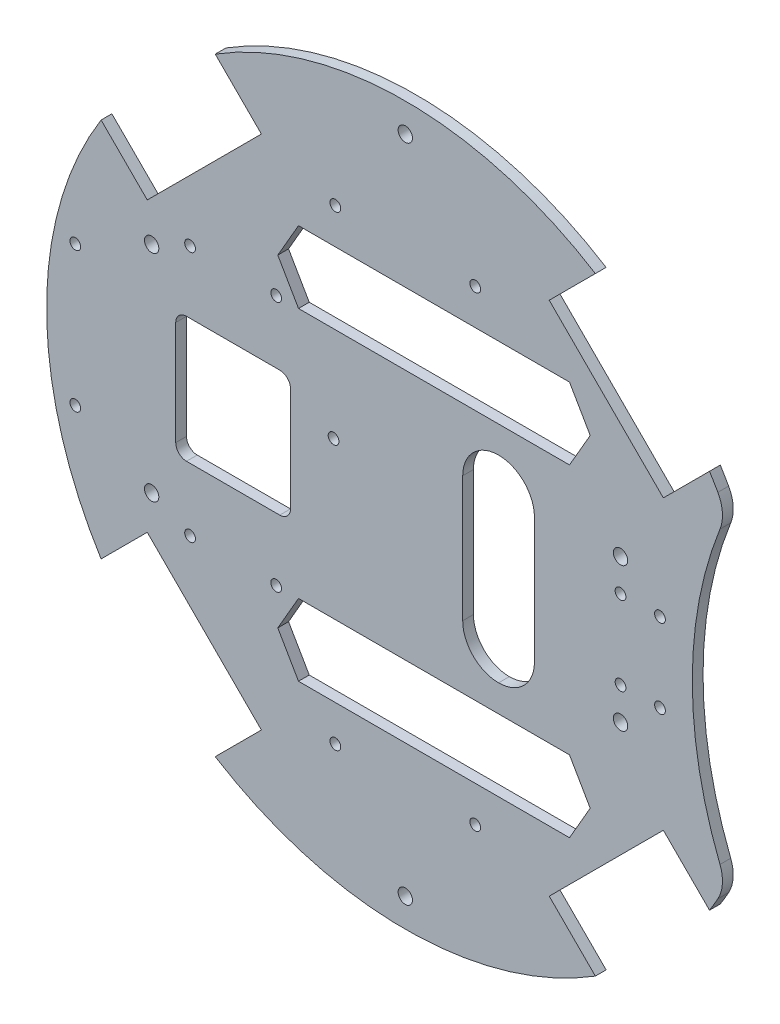
SolidWorks part; units mm, degrees
material "Caoba"
ref_plane "Alzado" through (0, 0, 0) normal (0, 0, 1) x (1, 0, 0)
ref_plane "Planta" through (0, 0, 0) normal (0, 1, 0) x (1, 0, 0)
ref_plane "Vista lateral" through (0, 0, 0) normal (1, 0, 0) x (0, 0, -1)
sketch "Croquis1" plane through (0, 0, 0) normal (0, 0, 1) x (1, 0, 0)
  circle A0 centre (0, 0) radius 100
  dimension "D1" = 200
extrude "Saliente-Extruir1" add sketch "Croquis1" along normal blind 3
sketch "Croquis3" plane through (0, 0, 3) normal (0, 0, 1) x (1, 0, 0)
  line L0 (0, 0) -> (190, 0) construction
  circle A0 centre (190, 0) radius 110
  dimension "D1" = 220
  dimension "D2" = 190
extrude "Cortar-Extruir1" cut sketch "Croquis3" against normal blind 3
fillet "Redondeo1" radius 10 2 edges at (89.4737, -44.6594, 1.5) (89.4737, 44.6594, 1.5)
sketch "Croquis7" plane through (0, 0, 3) normal (0, 0, 1) x (1, 0, 0)
  line L0 (-71.9393, -40.1195) -> (-40.1195, -71.9393)
  line L1 (-71.9393, -40.1195) -> (-89.617, -57.7972)
  line L2 (-40.1195, -71.9393) -> (-57.7972, -89.617)
  line L3 (-89.617, -57.7972) -> (-57.7972, -89.617)
  line L6 (0, -100) -> (0, 100) construction
  line L7 (-100, 0) -> (80, 0) construction
  line L8 (-40.1195, 71.9393) -> (-71.9393, 40.1195)
  line L9 (-40.1195, 71.9393) -> (-57.7972, 89.617)
  line L10 (-57.7972, 89.617) -> (-89.617, 57.7972)
  line L11 (-71.9393, 40.1195) -> (-89.617, 57.7972)
  line L12 (71.9393, 40.1195) -> (40.1195, 71.9393)
  line L13 (71.9393, 40.1195) -> (89.617, 57.7972)
  line L14 (89.617, 57.7972) -> (57.7972, 89.617)
  line L15 (40.1195, 71.9393) -> (57.7972, 89.617)
  line L16 (40.1195, -71.9393) -> (71.9393, -40.1195)
  line L17 (40.1195, -71.9393) -> (57.7972, -89.617)
  line L18 (57.7972, -89.617) -> (89.617, -57.7972)
  line L19 (71.9393, -40.1195) -> (89.617, -57.7972)
  line L20 (70.7107, -70.7107) -> (-70.7107, 70.7107) construction
  line L21 (-70.7107, -70.7107) -> (70.7107, 70.7107) construction
  arc A0 (87.1345, 49.0671) -> (87.1345, -49.0671) centre (0, 0) ccw construction
  arc A1 (87.1345, 49.0671) -> (87.1345, -49.0671) centre (0, 0) ccw construction
  arc A4 (87.7193, 40.4803) -> (87.7193, -40.4803) centre (190, 0) ccw construction
  point P24 (0, 0)
  dimension "D1" = 22.5
  dimension "D2" = 45
  dimension "D3" = 25
  dimension "D4" = 45
  dimension "D5" = 200
  dimension "D6" = 4
  dimension "D7" = 79.2376
  dimension "D8" = 22.5
  dimension "D9" = 200
  dimension "D10" = 45
  dimension "D11" = 90
  dimension "D12" = 79.2376
extrude "Cortar-Extruir3" cut sketch "Croquis7" against normal blind 10
sketch "Croquis10" plane through (0, 0, 3) normal (0, 0, 1) x (1, 0, 0)
  line L0 (80, 0) -> (-100, 0) construction
  circle A0 centre (-20, 8.5) radius 1.5
  arc A1 (-84.8075, 52.9877) -> (-84.8075, -52.9877) centre (0, 0) ccw construction
  arc A5 (87.7193, 40.4803) -> (87.7193, -40.4803) centre (190, 0) ccw construction
  dimension "D1" = 3
  dimension "D2" = 8.5
  dimension "D3" = 20
extrude "Cortar-Extruir4" cut sketch "Croquis10" against normal through all
sketch "Croquis12" plane through (0, 0, 0) normal (0, 0, -1) x (-1, 0, 0)
  line L0 (-80, 0) -> (100, 0) construction
  line L1 (-71, 0) -> (-71, -11) construction
  line L2 (-71, 0) -> (-71, 11) construction
  line L5 (-60, 11) -> (-60, -11) construction
  line L6 (0, 100) -> (0, -100) construction
  circle A4 centre (-71, 11) radius 1.5
  circle A6 centre (-71, -11) radius 1.5
  circle A7 centre (-60, 11) radius 1.5
  circle A8 centre (-60, -11) radius 1.5
  arc A9 (52.9877, 84.8075) -> (-52.9877, 84.8075) centre (0, 0) ccw construction
  arc A10 (-52.9877, -84.8075) -> (52.9877, -84.8075) centre (0, 0) ccw construction
  arc A11 (-87.7193, -40.4803) -> (-87.7193, 40.4803) centre (-190, 0) ccw construction
  arc A12 (84.8075, -52.9877) -> (84.8075, 52.9877) centre (0, 0) ccw construction
  dimension "D4" = 11
  dimension "D5" = 3
  dimension "D6" = 3
  dimension "D7" = 11
  dimension "D1" = 3
  dimension "D2" = 3
  dimension "D3" = 60
  dimension "D8" = 11
  dimension "D9" = 22
  dimension "D10" = 11
extrude "Cortar-Extruir6" cut sketch "Croquis12" against normal through all
sketch "Croquis13" plane through (0, 0, 0) normal (0, 0, -1) x (-1, 0, 0)
  line L0 (0, 100) -> (0, -100) construction
  line L1 (100, 0) -> (-100, 0) construction
  line L2 (-70.7107, -70.7107) -> (70.7107, 70.7107) construction
  line L3 (-70.7093, 70.7093) -> (70.712, -70.712) construction
  line L4 (-70.7093, 70.7093) -> (-70.7107, -70.7107) construction
  line L5 (-70.7107, -70.7107) -> (70.712, -70.712) construction
  line L6 (70.712, -70.712) -> (70.7107, 70.7107) construction
  line L7 (70.7107, 70.7107) -> (-70.7093, 70.7093) construction
  arc A0 (52.9877, 84.8075) -> (-52.9877, 84.8075) centre (0, 0) ccw construction
  arc A1 (-52.9877, -84.8075) -> (52.9877, -84.8075) centre (0, 0) ccw construction
  arc A2 (84.8075, -52.9877) -> (84.8075, 52.9877) centre (0, 0) ccw construction
  circle A3 centre (0, 92) radius 2
  circle A4 centre (0, -92) radius 2
  circle A7 centre (70.7111, 30) radius 2
  circle A8 centre (70.7116, -30) radius 2
  circle A11 centre (-60, 20) radius 2
  circle A12 centre (-60, -20) radius 2
  dimension "D10" = 4
  dimension "D11" = 92
  dimension "D12" = 4
  dimension "D13" = 92
  dimension "D14" = 4
  dimension "D15" = 4
  dimension "D16" = 30
  dimension "D17" = 30
  dimension "D18" = 4
  dimension "D19" = 4
  dimension "D20" = 20
  dimension "D21" = 20
  dimension "D22" = 60
  dimension "D23" = 60
  dimension "D1" = 200
  dimension "D2" = 0
  dimension "D3" = 0
  dimension "D4" = 200
  dimension "D5" = 200
  dimension "D6" = 45
  dimension "D7" = 45
  dimension "D8" = 141.42
  dimension "D9" = 141.42
extrude "Cortar-Extruir7" cut sketch "Croquis13" against normal through all
sketch "Croquis15" plane through (0, 0, 0) normal (0, 0, -1) x (-1, 0, 0)
  line L0 (0, -100) -> (0, 100) construction
  line L1 (-40, 55) -> (24, 55)
  line L2 (-40, 55) -> (-40, 35)
  line L3 (-40, 35) -> (24, 35)
  line L4 (24, 55) -> (24, 35)
  line L5 (100, 0) -> (-80, 0) construction
  line L6 (29.7735, -35) -> (35.547, -45)
  line L7 (-51.547, 45) -> (-45.7735, 35)
  line L8 (-45.7735, 35) -> (-34.2265, 35)
  line L9 (-34.2265, 35) -> (-28.453, 45)
  line L10 (-28.453, 45) -> (-34.2265, 55)
  line L11 (-34.2265, 55) -> (-45.7735, 55)
  line L12 (-45.7735, 55) -> (-51.547, 45)
  line L13 (35.547, 45) -> (29.7735, 55)
  line L14 (29.7735, 55) -> (18.2265, 55)
  line L15 (18.2265, 55) -> (12.453, 45)
  line L16 (12.453, 45) -> (18.2265, 35)
  line L17 (18.2265, 35) -> (29.7735, 35)
  line L18 (29.7735, 35) -> (35.547, 45)
  line L19 (18.2265, -35) -> (29.7735, -35)
  line L20 (12.453, -45) -> (18.2265, -35)
  line L21 (18.2265, -55) -> (12.453, -45)
  line L22 (29.7735, -55) -> (18.2265, -55)
  line L23 (35.547, -45) -> (29.7735, -55)
  line L24 (-45.7735, -55) -> (-51.547, -45)
  line L25 (-34.2265, -55) -> (-45.7735, -55)
  line L26 (-28.453, -45) -> (-34.2265, -55)
  line L27 (-34.2265, -35) -> (-28.453, -45)
  line L28 (-45.7735, -35) -> (-34.2265, -35)
  line L29 (-51.547, -45) -> (-45.7735, -35)
  line L30 (-40, -35) -> (24, -35)
  line L31 (24, -55) -> (24, -35)
  line L32 (-40, -55) -> (24, -55)
  line L33 (-40, -55) -> (-40, -35)
  line L35 (32, 17.5) -> (64, 17.5)
  line L36 (32, 17.5) -> (32, -17.5)
  line L37 (32, -17.5) -> (64, -17.5)
  line L38 (64, 17.5) -> (64, -17.5)
  arc A0 (-52.9877, -84.8075) -> (52.9877, -84.8075) centre (0, 0) ccw construction
  arc A1 (52.9877, 84.8075) -> (-52.9877, 84.8075) centre (0, 0) ccw construction
  arc A2 (84.8075, -52.9877) -> (84.8075, 52.9877) centre (0, 0) ccw construction
  arc A3 (-87.7193, -40.4803) -> (-87.7193, 40.4803) centre (-190, 0) ccw construction
  circle A4 centre (-40, 45) radius 10 construction
  circle A5 centre (24, 45) radius 10 construction
  dimension "D1" = 35
  dimension "D2" = 64
  dimension "D3" = 20
  dimension "D4" = 40
  dimension "D5" = 0
  dimension "D6" = 0
  dimension "D7" = 35
  dimension "D8" = 32
  dimension "D9" = 17.5
  dimension "D10" = 32
extrude "Cortar-Extruir8" cut sketch "Croquis15" against normal through all contours L16 L15 L1 L10 L9 L3 | L9 L10 L1 L2 L3 | L11 L12 L7 L8 L2 | L17 L18 L13 L14 L4 | L15 L16 L3 L4 L1 | L26 L32 L21 L20 L30 L27 | L22 L31 L19 L20 L21 | L31 L22 L23 L6 L19 | L33 L25 L26 L27 L28 | L25 L33 L28 L29 L24 | L38 L35 L36 L37 | L36 L35 L38 L37 region at (35.5095, 45, 0) region at (44.4905, 45, 0) region at (8, 45, 0) region at (-19.5095, 45, 0) region at (-28.4905, 45, 0) region at (-28.4905, -45, 0) region at (-19.5095, -45, 0) region at (8, -45, 0) region at (35.5095, -45, 0) region at (44.4905, -45, 0) region at (-48, 0, 0)
fillet "Redondeo2" radius 3 4 edges at (-64, -17.5, 1.5) (-32, -17.5, 1.5) (-64, 17.5, 1.5) (-32, 17.5, 1.5)
sketch "Croquis16" plane through (0, 0, 0) normal (0, 0, -1) x (-1, 0, 0)
  line L0 (0, 100) -> (0, -100) construction
  line L1 (100, 0) -> (-80, 0) construction
  line L2 (36, 35) -> (60, 35) construction
  line L3 (60, 35) -> (60, -35) construction
  line L4 (60, -35) -> (36, -35) construction
  line L5 (36, -35) -> (36, 35) construction
  arc A0 (52.9877, 84.8075) -> (-52.9877, 84.8075) centre (0, 0) ccw construction
  arc A1 (-52.9877, -84.8075) -> (52.9877, -84.8075) centre (0, 0) ccw construction
  arc A2 (84.8075, -52.9877) -> (84.8075, 52.9877) centre (0, 0) ccw construction
  arc A3 (-87.7193, -40.4803) -> (-87.7193, 40.4803) centre (-190, 0) ccw construction
  circle A4 centre (-19.5, 65) radius 1.5
  circle A5 centre (19.5, 65) radius 1.5
  circle A6 centre (19.5, -65) radius 1.5
  circle A7 centre (-19.5, -65) radius 1.5
  circle A8 centre (36, 35) radius 1.5
  circle A9 centre (36, -35) radius 1.5
  circle A10 centre (60, -35) radius 1.5
  circle A11 centre (60, 35) radius 1.5
  circle A14 centre (92, 19.5) radius 1.5
  circle A15 centre (92, -19.5) radius 1.5
  dimension "D1" = 3
  dimension "D2" = 3
  dimension "D3" = 39
  dimension "D4" = 19.5
  dimension "D5" = 65
  dimension "D6" = 65
  dimension "D7" = 70
  dimension "D8" = 24
  dimension "D9" = 40
  dimension "D10" = 35
  dimension "D15" = 3
  dimension "D16" = 3
  dimension "D17" = 3
  dimension "D18" = 3
  dimension "D25" = 3
  dimension "D26" = 3
  dimension "D27" = 19.5
  dimension "D28" = 19.5
  dimension "D29" = 92
  dimension "D30" = 92
extrude "Cortar-Extruir9" cut sketch "Croquis16" against normal through all
sketch "Croquis17" plane through (0, 0, 0) normal (0, 0, -1) x (-1, 0, 0)
  line L0 (20, 7) -> (-16, 7) construction
  line L1 (-16, 0) -> (-16, 27.5) construction
  line L2 (0, 0) -> (-16, 0) construction
  line L4 (-16, 27.5) -> (-36, 27.5)
  line L5 (-16, 27.5) -> (-16, -27.5)
  line L6 (-16, -27.5) -> (-36, -27.5)
  line L7 (-36, 27.5) -> (-36, -27.5)
  circle A0 centre (20, 8.5) radius 1.5 construction
  arc A1 (-87.7193, -40.4803) -> (-87.7193, 40.4803) centre (-190, 0) ccw construction
  dimension "D1" = 55
  dimension "D2" = 27.5
  dimension "D3" = 20
  dimension "D4" = 36
  dimension "D5" = 154
extrude "Cortar-Extruir10" cut sketch "Croquis17" against normal through all
fillet "Redondeo3" radius 10 4 edges at (16, -27.5, 1.5) (36, -27.5, 1.5) (16, 27.5, 1.5) (36, 27.5, 1.5)
